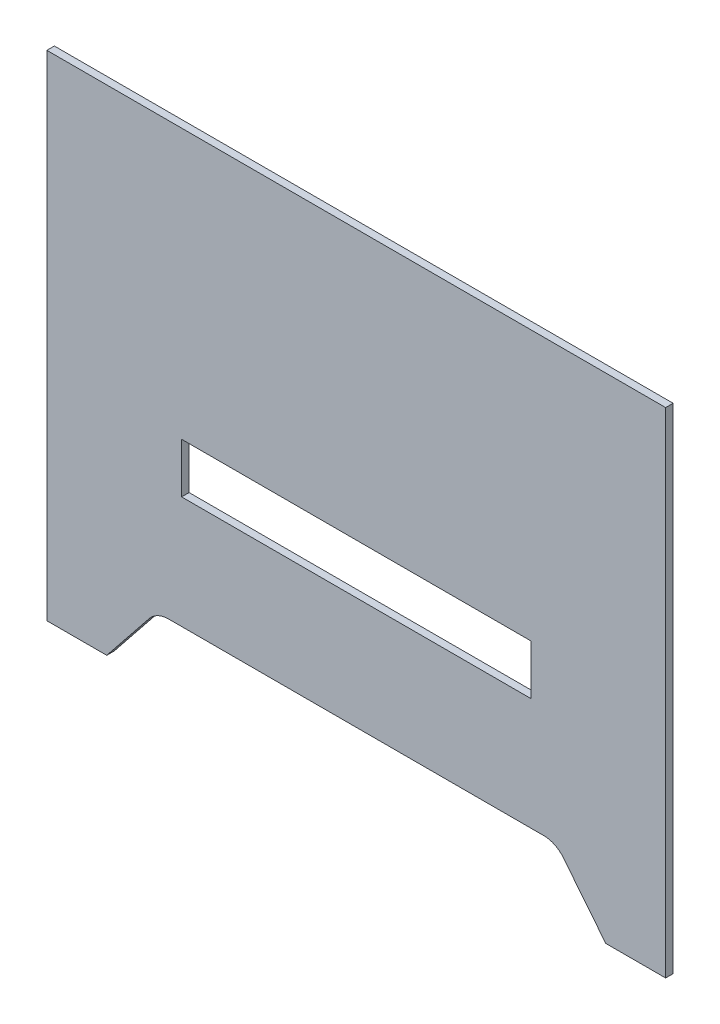
SolidWorks part; units mm, degrees
ref_plane "前视基准面" through (0, 0, 0) normal (0, 0, 1) x (1, 0, 0)
ref_plane "上视基准面" through (0, 0, 0) normal (0, 1, 0) x (1, 0, 0)
ref_plane "右视基准面" through (0, 0, 0) normal (1, 0, 0) x (0, 0, -1)
sketch "Sketch1" plane through (0, 0, 0) normal (0, 0, 1) x (1, 0, 0)
  line L0 (0, -99) -> (0, 0) construction
  line L1 (-124, -99) -> (124, -99) construction
  line L2 (-124, -99) -> (-124, 99)
  line L3 (-124, 99) -> (124, 99)
  line L4 (124, -99) -> (124, 99)
  line L5 (-124, -99) -> (124, 99) construction
  line L6 (-124, 99) -> (124, -99) construction
  line L7 (-75.1938, -74) -> (75.1938, -74)
  line L8 (83.0024, -77.753) -> (100, -99)
  line L9 (100, -99) -> (124, -99)
  line L10 (-100, -99) -> (-124, -99)
  line L11 (-83.0024, -77.753) -> (-100, -99)
  line L13 (-70, -29) -> (70, -29)
  line L14 (-70, -29) -> (-70, -9)
  line L15 (-70, -9) -> (70, -9)
  line L16 (70, -29) -> (70, -9)
  line L17 (-70, -29) -> (70, -9) construction
  line L18 (-70, -9) -> (70, -29) construction
  arc A0 (83.0024, -77.753) -> (75.1938, -74) centre (75.1938, -84) ccw
  arc A1 (-83.0024, -77.753) -> (-75.1938, -74) centre (-75.1938, -84) cw
  point P0 (0, 0)
  point P8 (0, -19)
  point P13 (80, -74)
  point P18 (0, -74)
  dimension "D6" = 10
  dimension "D1" = 248
  dimension "D2" = 198
  dimension "D3" = 25
  dimension "D4" = 24
  dimension "D5" = 80
  dimension "D7" = 140
  dimension "D8" = 20
  dimension "D9" = 108
extrude "Boss-Extrude1" add sketch "Sketch1" along normal blind 3
